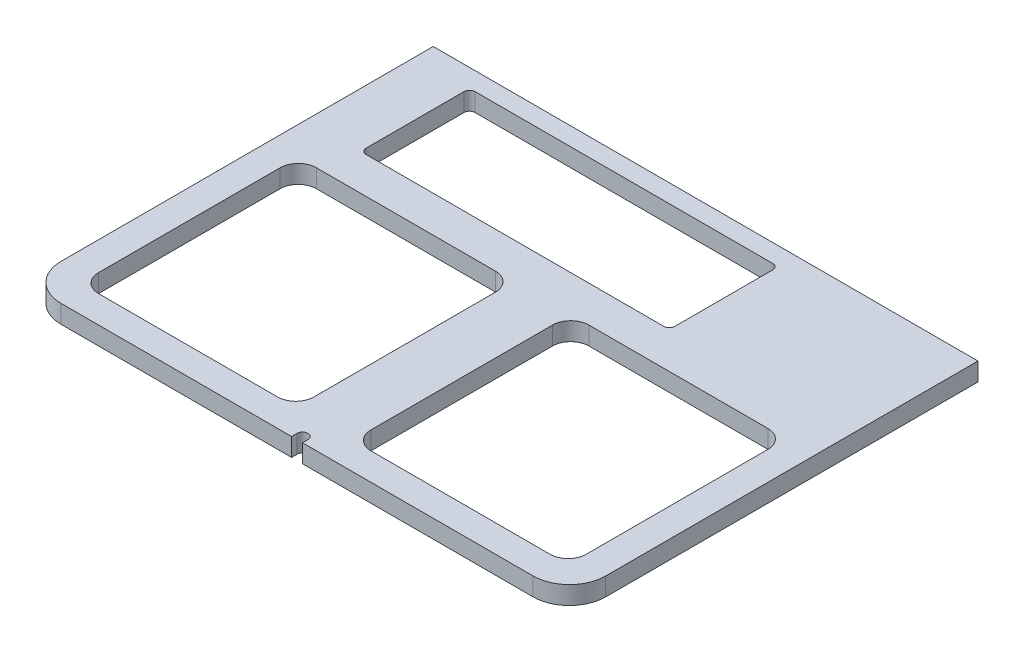
SolidWorks part; units mm, degrees
ref_plane "Ebene vorne" through (0, 0, 0) normal (0, 0, 1) x (1, 0, 0)
ref_plane "Ebene oben" through (0, 0, 0) normal (0, 1, 0) x (1, 0, 0)
ref_plane "Ebene rechts" through (0, 0, 0) normal (1, 0, 0) x (0, 0, -1)
sketch "Skizze1" plane through (0, 10, 0) normal (0, 1, 0) x (1, 0, 0)
  line L0 (0, -75) -> (130, -75)
  line L2 (0, -75) -> (0, 75.7029)
  line L3 (0, 75.7029) -> (150, 75.7029) construction
  line L4 (150, -55) -> (150, 75.7029)
  line L5 (150, -55) -> (150, 150) construction
  line L6 (15.7029, -60) -> (15.7029, -75.7029) construction
  line L7 (15.7029, 60) -> (134.2971, 60)
  line L8 (15.7029, 60) -> (15.7029, -60)
  line L9 (15.7029, -60) -> (134.2971, -60)
  line L10 (134.2971, 60) -> (134.2971, -60)
  line L11 (15.7029, -75.7029) -> (15.7029, -60) construction
  line L12 (0, -60) -> (15.7029, -60) construction
  line L13 (134.2971, 60) -> (134.2971, 75.7029) construction
  line L14 (134.2971, 60) -> (150, 60) construction
  line L15 (150, 75.7029) -> (150, 150)
  line L16 (150, 150) -> (0, 150)
  line L17 (0, 150) -> (0, 75.7029)
  arc A0 (130, -75) -> (150, -55) centre (130, -55) ccw
  arc A1 (130, -75) -> (150, -55) centre (130, -55) ccw construction
  dimension "D1" = 120
extrude "Linear austragen1" add sketch "Skizze1" along normal blind 10
fillet "Verrundung2" radius 10 4 edges at (15.7029, 15, 60) (134.2971, 15, 60) (134.2971, 15, -60) (15.7029, 15, -60)
mirror "Spiegeln1" about plane through (0, 20, -150) normal (1, 0, 0) of "Verrundung2", "Linear austragen1"
sketch "Skizze3" plane through (0, 10, 0) normal (0, -1, 0) x (1, 0, 0)
  line L0 (-150, 55) -> (-150, -150) construction
  line L1 (-120, -80) -> (50, -80)
  line L2 (-120, -80) -> (-120, -140)
  line L3 (-120, -140) -> (50, -140)
  line L4 (50, -80) -> (50, -140)
  line L5 (150, -150) -> (-150, -150) construction
  line L6 (0, -60.4164) -> (0, -150) construction
  dimension "D1" = 30
  dimension "D2" = 10
  dimension "D3" = 50
  dimension "D4" = 60
extrude "Schnitt-Linear austragen1" cut sketch "Skizze3" against normal blind 10
fillet "Verrundung3" radius 3 4 edges at (-120, 15, -140) (50, 15, -140) (50, 15, -80) (-120, 15, -80)
sketch "Skizze4" plane through (0, 10, 0) normal (0, -1, 0) x (1, 0, 0)
  line L0 (-3.0001, 75) -> (-3.0001, 72)
  line L1 (-130, 75) -> (130, 75) construction
  line L2 (-3.0001, 75) -> (2.9825, 75)
  line L3 (2.9825, 75) -> (2.9999, 72.0175)
  arc A0 (-3.0001, 72) -> (2.9999, 72.0175) centre (-0.0001, 72) ccw
  dimension "D2" = 3
  dimension "D1" = 3
extrude "Schnitt-Linear austragen2" cut sketch "Skizze4" against normal blind 10
